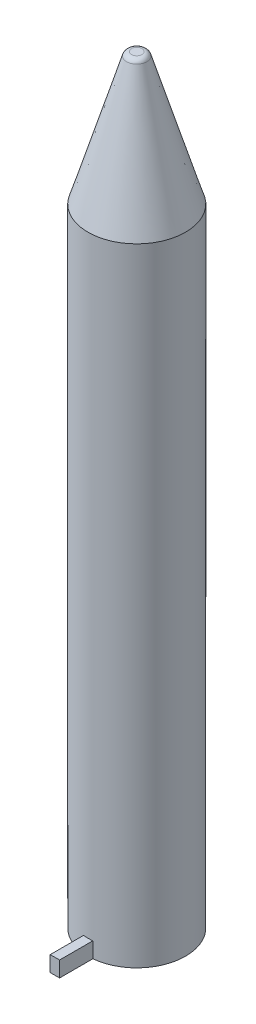
SolidWorks part; units mm, degrees
ref_plane "Front Plane" through (0, 0, 0) normal (0, 0, 1) x (1, 0, 0)
ref_plane "Top Plane" through (0, 0, 0) normal (0, 1, 0) x (1, 0, 0)
ref_plane "Right Plane" through (0, 0, 0) normal (1, 0, 0) x (0, 0, -1)
sketch "Sketch1" plane through (0, 0, 0) normal (0, 1, 0) x (1, 0, 0)
  circle A0 centre (0, 0) radius 9.398
  dimension "D1" = 18.796
extrude "Boss-Extrude1" add sketch "Sketch1" along normal blind 120.65
sketch "Sketch2" plane through (0, 0, 0) normal (0, 0, 1) x (1, 0, 0)
  line L8 (0, 120.65) -> (0, 146.05)
  line L9 (9.398, 120.65) -> (-9.398, 120.65) construction
  line L10 (1.9575, 145.3386) -> (9.398, 120.65)
  line L11 (9.398, 120.65) -> (0, 120.65)
  line L12 (1, 146.05) -> (0, 146.05)
  arc A3 (1, 146.05) -> (1.9575, 145.3386) centre (1, 145.05) cw
  dimension "D2" = 25.4
  dimension "D1" = 1
revolve "Revolve1" add sketch "Sketch2" angle 360 about L8
sketch "Sketch3" plane through (0, 0, 0) normal (0, -1, 0) x (1, 0, 0)
  line L1 (-0.9, 15.75) -> (0.9, 15.75)
  line L2 (-0.9, 15.75) -> (-0.9, 9.3548)
  line L4 (0.9, 15.75) -> (0.9, 9.3548)
  arc A0 (0.9, 9.3548) -> (-0.9, 9.3548) centre (0, 0) ccw
  dimension "D1" = 0.9
  dimension "D3" = 15.75
extrude "Boss-Extrude2" add sketch "Sketch3" against normal blind 3
